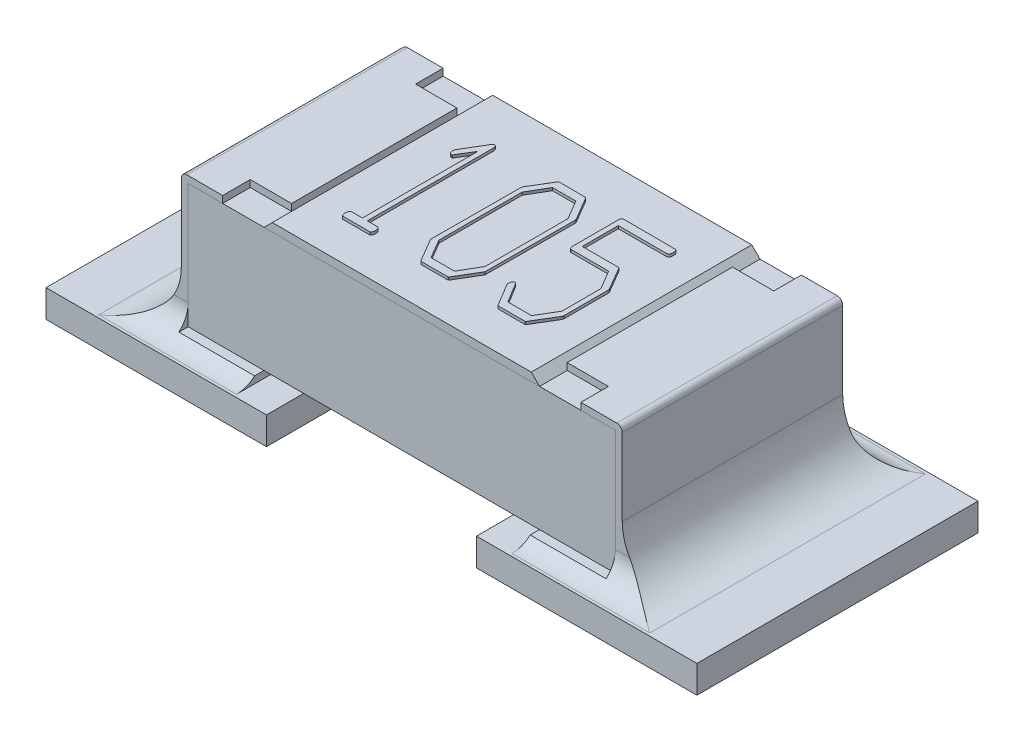
SolidWorks part; units mm, degrees
material "Ceramic Porcelain"
ref_plane "Front Plane" through (0, 0, 0) normal (0, 0, 1) x (1, 0, 0)
ref_plane "Top Plane" through (0, 0, 0) normal (0, 1, 0) x (1, 0, 0)
ref_plane "Right Plane" through (0, 0, 0) normal (1, 0, 0) x (0, 0, -1)
sketch "Sketch1" plane through (0, 0, 0) normal (1, 0, 0) x (0, 0, -1)
  line L0 (0, 55) -> (0, -55) construction
  line L1 (-0.4, 0.575) -> (0.4, 0.575)
  line L2 (-0.4, 0.575) -> (-0.4, 0.125)
  line L3 (-0.4, 0.125) -> (0.4, 0.125)
  line L4 (0.4, 0.575) -> (0.4, 0.125)
  line L5 (55, 0) -> (-55, 0) construction
  dimension "D1" = 0.8
  dimension "D2" = 0.4
  dimension "D3" = 0.45
  dimension "D4" = 0.125
extrude "Boss-Extrude1" add sketch "Sketch1" along normal mid plane 1.55
sketch "Sketch2" plane through (0, 0, 0) normal (0, 0, 1) x (1, 0, 0)
  line L0 (-0.5, 0.6) -> (-0.78, 0.6)
  line L1 (-0.8, 0.58) -> (-0.8, 0.1)
  line L2 (-0.8, 0.1) -> (-0.5, 0.1)
  line L3 (-0.5, 0.1) -> (-0.5, 0.125)
  line L4 (0.775, 0.125) -> (-0.775, 0.125) construction
  line L5 (-0.5, 0.125) -> (-0.775, 0.125)
  line L6 (-0.775, 0.125) -> (-0.775, 0.575)
  line L7 (-0.775, 0.575) -> (-0.5, 0.575)
  line L8 (0.775, 0.575) -> (-0.775, 0.575) construction
  line L9 (-0.5, 0.575) -> (-0.5, 0.6)
  line L11 (0.5, 0.575) -> (0.5, 0.6)
  line L12 (0.5, 0.6) -> (0.78, 0.6)
  line L13 (0.8, 0.58) -> (0.8, 0.1)
  line L14 (0.8, 0.1) -> (0.5, 0.1)
  line L15 (0.5, 0.1) -> (0.5, 0.125)
  line L16 (0.5, 0.125) -> (0.775, 0.125)
  line L17 (0.775, 0.125) -> (0.775, 0.575)
  line L18 (0.775, 0.575) -> (0.5, 0.575)
  arc A0 (0.78, 0.6) -> (0.8, 0.58) centre (0.78, 0.58) cw
  arc A1 (-0.78, 0.6) -> (-0.8, 0.58) centre (-0.78, 0.58) ccw
  point P28 (-0.8, 0.6)
  dimension "D6" = 0.02
  dimension "D1" = 0.025
  dimension "D2" = 0.025
  dimension "D3" = 0.025
  dimension "D4" = 0.3
  dimension "D5" = 0.3
extrude "Boss-Extrude2" add sketch "Sketch2" along normal mid plane 0.8 separate body
sketch "Sketch3" plane through (0, 0.6, 0) normal (0, 1, 0) x (1, 0, 0)
  line L0 (0.5, -0.4) -> (0.5, 0.4) construction
  line L1 (-0.5, 0.4) -> (-0.65, 0.4)
  line L2 (-0.5, 0.4) -> (-0.5, 0.3)
  line L3 (-0.5, 0.3) -> (-0.65, 0.3)
  line L4 (-0.65, 0.4) -> (-0.65, 0.3)
  line L5 (-0.5, -0.4) -> (-0.65, -0.4)
  line L6 (-0.5, -0.4) -> (-0.5, -0.3)
  line L7 (-0.5, -0.3) -> (-0.65, -0.3)
  line L8 (-0.65, -0.4) -> (-0.65, -0.3)
  line L9 (0.5, -0.4) -> (0.65, -0.4)
  line L10 (0.5, -0.4) -> (0.5, -0.3)
  line L11 (0.5, -0.3) -> (0.65, -0.3)
  line L12 (0.65, -0.4) -> (0.65, -0.3)
  line L13 (0.775, -0.4) -> (-0.775, -0.4) construction
  line L15 (0.5, 0.4) -> (0.65, 0.4)
  line L16 (0.5, 0.4) -> (0.5, 0.3)
  line L17 (0.5, 0.3) -> (0.65, 0.3)
  line L18 (0.65, 0.4) -> (0.65, 0.3)
  dimension "D1" = 0.15
  dimension "D2" = 0.1
extrude "Cut-Extrude1" cut sketch "Sketch3" against normal blind 0.025
sketch "Sketch4" plane through (0, 0, 0) normal (0, 0, 1) x (1, 0, 0)
  line L0 (-0.5, 0.575) -> (0.5, 0.575)
  line L1 (0.5, 0.575) -> (0.47, 0.605)
  line L2 (0.47, 0.605) -> (-0.47, 0.605)
  line L3 (-0.47, 0.605) -> (-0.5, 0.575)
  dimension "D1" = 45
  dimension "D2" = 45
  dimension "D3" = 0.03
extrude "Boss-Extrude3" add sketch "Sketch4" along normal mid plane 0.8 separate body
sketch "Sketch6" plane through (0, 0.605, 0) normal (0, 1, 0) x (1, 0, 0)
  line L0 (-0.4, -0.25) -> (0.4, -0.25) construction
  line L1 (0, -0.2777) -> (0, 0.2777) construction
  line L2 (-0.2777, 0) -> (0.2777, 0) construction
  text T0 "105" font "SWMono" height 0.5
  dimension "D1" = 0.8
  dimension "D2" = 0.4
  dimension "D3" = 0.25
extrude "Boss-Extrude4" add sketch "Sketch6" along normal blind 0.01
sketch "Sketch7" plane through (0, 0, 0) normal (0, 1, 0) x (1, 0, 0)
  line L0 (0, -0.2833) -> (0, 0.2833) construction
  line L1 (-0.381, -0.51) -> (-1.181, -0.51)
  line L2 (-0.381, -0.51) -> (-0.381, 0.51)
  line L3 (-0.381, 0.51) -> (-1.181, 0.51)
  line L4 (-1.181, -0.51) -> (-1.181, 0.51)
  line L5 (0.381, -0.51) -> (1.181, -0.51)
  line L6 (0.381, -0.51) -> (0.381, 0.51)
  line L7 (0.381, 0.51) -> (1.181, 0.51)
  line L8 (1.181, -0.51) -> (1.181, 0.51)
  line L9 (-0.2833, 0) -> (0.2833, 0) construction
  dimension "D1" = 0.8
  dimension "D2" = 0.381
  dimension "D3" = 0.381
  dimension "D4" = 1.02
  dimension "D5" = 0.51
extrude "Boss-Extrude5" add sketch "Sketch7" along normal blind 0.1
fillet "Fillet3" radius 0.2 1 edges at (-0.8, 0.1, 0)
fillet "Fillet4" radius 0.2 1 edges at (0.8, 0.1, 0)
fillet "Fillet5" radius 0.1 2 edges at (0.75, 0.1, -0.4) (0.75, 0.1, 0.4)
fillet "Fillet6" radius 0.1 2 edges at (-0.75, 0.1, 0.4) (-0.75, 0.1, -0.4)
